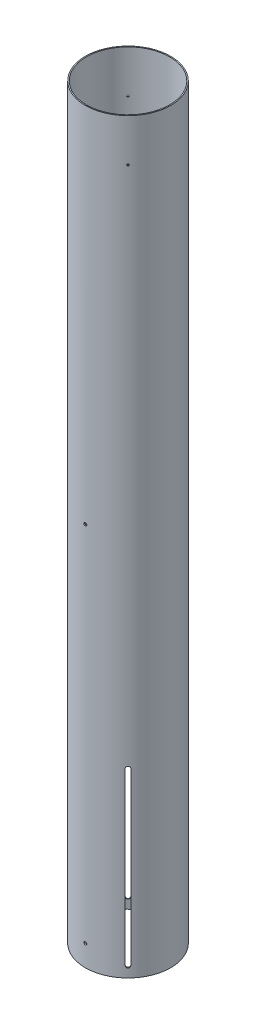
SolidWorks part; units mm, degrees
material "Wildman Fiberglass"
ref_plane "Front Plane" through (0, 0, 0) normal (0, 0, 1) x (1, 0, 0)
ref_plane "Top Plane" through (0, 0, 0) normal (0, 1, 0) x (1, 0, 0)
ref_plane "Right Plane" through (0, 0, 0) normal (1, 0, 0) x (0, 0, -1)
sketch "Sketch1" plane through (0, 0, 0) normal (0, 1, 0) x (1, 0, 0)
  circle A0 centre (0, 0) radius 49.53
  circle A1 centre (0, 0) radius 50.8
  dimension "D1" = 101.6
  dimension "D2" = 99.06
extrude "Boss-Extrude1" add sketch "Sketch1" along normal blind 889
extrude "Cut-Extrude1" cut sketch "Sketch2" against normal blind 152.4
sketch "Sketch2" plane through (14.4921, 1243.3556, -192.6285) normal (0.7071, 0, -0.7071) x (0, 1, 0)
  line L0 (-1230.6556, 128.3427) -> (-1027.4556, 128.3427)
  line L1 (-1027.4556, 123.5802) -> (-1230.6556, 123.5802)
  arc A0 (-1230.6556, 128.3427) -> (-1230.6556, 123.5802) centre (-1230.6556, 125.9615) ccw
  arc A1 (-1027.4556, 128.3427) -> (-1027.4556, 123.5802) centre (-1027.4556, 125.9615) cw
pattern_circular "CirPattern1" count 4 over 360 about axis through (0, 889, 0) along (0, -1, 0) of "Cut-Extrude1" reverse direction yes
extrude "Cut-Extrude2" cut sketch "Sketch3" against normal blind 11.684
sketch "Sketch3" plane through (271.0916, 1243.3556, 52.3875) normal (0, 0, 1) x (-1, 0, 0)
  circle A0 centre (271.0916, 1217.9556) radius 1.7653
  circle A2 centre (271.0916, 786.1556) radius 1.7653
extrude "Cut-Extrude3" cut sketch "Sketch4" against normal blind 25.4
sketch "Sketch4" plane through (120.5803, 708.4046, -48.7382) normal (0.7071, 0, 0.7071) x (-0.7071, 0, 0.7071)
  line L0 (68.9263, -129.7954) -> (170.5263, -129.7954) construction
  circle A0 centre (119.7263, -129.7954) radius 1.0922
pattern_circular "CirPattern2" count 2 over 360 about axis through (0, 889, 0) along (0, -1, 0) of "Cut-Extrude3"
equation "\"Length\"=35"
equation "\"D1@Boss-Extrude1\"=\"Length\""
